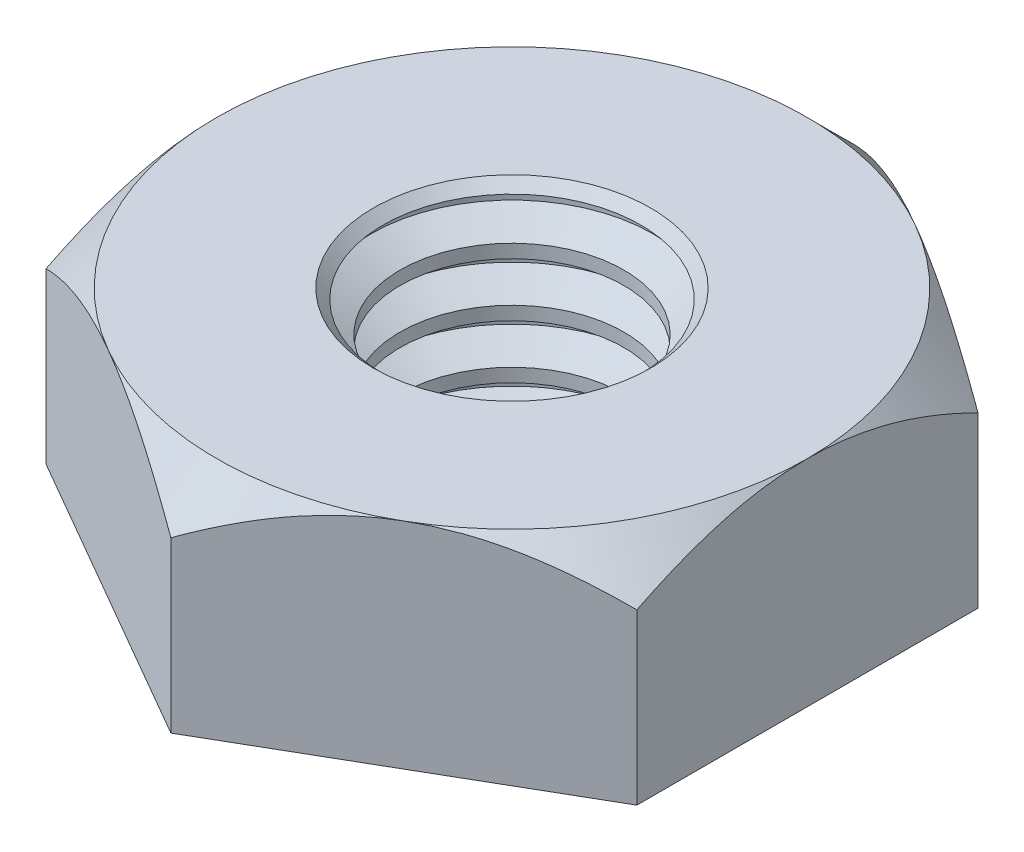
SolidWorks part; units mm, degrees
ref_plane "Front" through (0, 0, 0) normal (0, 0, 1) x (1, 0, 0)
ref_plane "Top" through (0, 0, 0) normal (0, 1, 0) x (1, 0, 0)
ref_plane "Right" through (0, 0, 0) normal (1, 0, 0) x (0, 0, -1)
sketch "Sketch1" plane through (0, 0, 0) normal (0, 1, 0) x (1, 0, 0)
  line L1 (0, 5.041) -> (-4.3656, 2.5205)
  line L2 (-4.3656, 2.5205) -> (-4.3656, -2.5205)
  line L3 (-4.3656, -2.5205) -> (0, -5.041)
  line L4 (0, -5.041) -> (4.3656, -2.5205)
  line L5 (4.3656, -2.5205) -> (4.3656, 2.5205)
  line L6 (4.3656, 2.5205) -> (0, 5.041)
  circle A0 centre (0, 0) radius 4.3656 construction
  dimension "Hex Flats" = 8.7312
extrude "Extrude1" add sketch "Sketch1" along normal blind 3.175
sketch "Sketch3" plane through (0, 0, 0) normal (1, 0, 0) x (0, 0, -1)
  line L0 (4.3656, 3.175) -> (5.041, 2.4996)
  line L1 (2.5205, 3.175) -> (5.041, 3.175) construction
  line L2 (5.041, 3.175) -> (5.041, 0) construction
  line L3 (5.041, 2.4996) -> (5.041, 3.175)
  line L4 (5.041, 3.175) -> (4.3656, 3.175)
  line L5 (0, 0.542) -> (0, -0.542) construction
  dimension "D1" = 45
  dimension "D2" = 8.7312
revolve "Cut-Revolve2" cut sketch "Sketch3" angle 360 about L5
sketch "Sketch2" plane through (0, 0, 0) normal (0, 0, 1) x (1, 0, 0)
  line L0 (0, 1.6636) -> (0, -0.3796) construction
  line L1 (0, 3.175) -> (1.6532, 3.175)
  line L3 (0, 3.175) -> (4.3656, 3.175) construction
  line L4 (0, 2.3812) -> (1.6532, 2.3812)
  line L5 (1.6532, 3.175) -> (2.0828, 2.927)
  line L6 (2.0828, 2.927) -> (2.0828, 2.8277)
  line L7 (2.0828, 2.8277) -> (1.6532, 2.5797)
  line L9 (1.6532, 2.3812) -> (1.6532, 2.5797)
  line L10 (0, 2.3812) -> (0, 3.175)
  line L11 (1.6532, 3.175) -> (1.6532, 2.5797) construction
  line L12 (2.0828, 2.8773) -> (1.6532, 2.8773) construction
  dimension "D1" = 60
  dimension "D2" = 0.1984
  dimension "D5" = 0.0992
  dimension "Pitch" = 0.7937
  dimension "Major Dia." = 4.1656
revolve "Cut-Revolve1" cut sketch "Sketch2" angle 360 about L0
pattern_linear "LPattern2" count 5 spacing 0.7937 along (0, -1, 0) of "Cut-Revolve1"
chamfer "Chamfer1" distance 0.3969 angle 45 1 edges at (0, 3.175, 1.6532) first distance on face at (0, 3.175, 0)
equation "\"D5@Sketch2\"=\"Pitch@Sketch2\"/8"
equation "\"D2@Sketch2\"=\"Pitch@Sketch2\"/4"
equation "\"D3@LPattern2\"=\"Pitch@Sketch2\""
equation "\"D1@LPattern2\"=(\"Height@Extrude1\"/\"Pitch@Sketch2\")+0.5"
equation "\"D2@Sketch3\"=\"Hex Flats@Sketch1\""
equation "\"D1@Chamfer1\"=\"Pitch@Sketch2\"/2"
